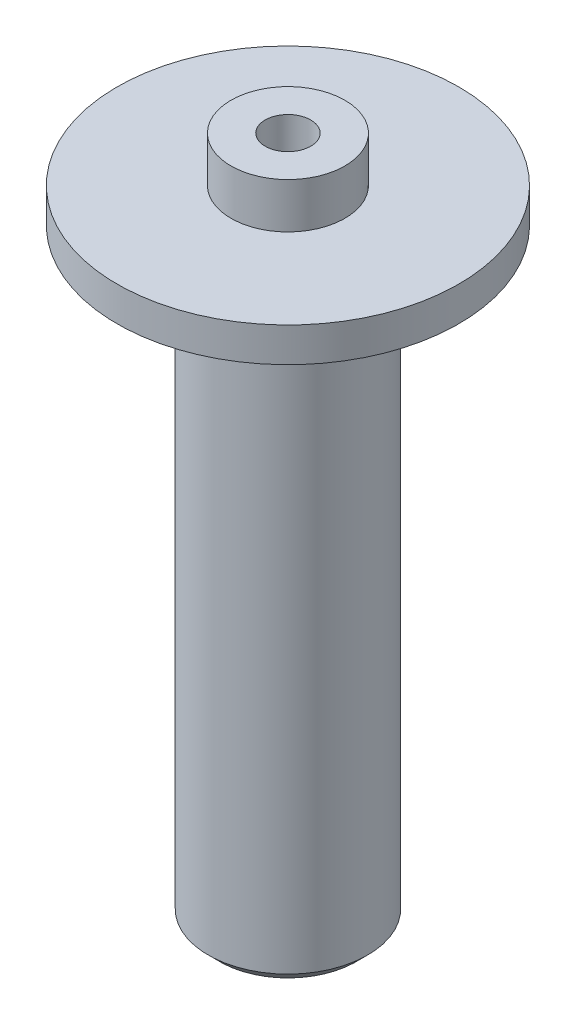
SolidWorks part; units mm, degrees
ref_plane "Спереди" through (0, 0, 0) normal (0, 0, 1) x (1, 0, 0)
ref_plane "Сверху" through (0, 0, 0) normal (0, 1, 0) x (1, 0, 0)
ref_plane "Справа" through (0, 0, 0) normal (1, 0, 0) x (0, 0, -1)
sketch "Эскиз1" plane through (0, 0, 0) normal (0, 0, 1) x (1, 0, 0)
  line L0 (2, 0) -> (2, 60)
  line L1 (2, 60) -> (5, 60)
  line L4 (5, 60) -> (5, 56.0159)
  line L5 (5, 56.0159) -> (15, 56.0159)
  line L6 (15, 56.0159) -> (15, 52.9943)
  line L7 (15, 52.9943) -> (7, 52.9943)
  line L8 (7, 52.9943) -> (7, 0)
  line L10 (7, 0) -> (2, 0)
  line L11 (0, -11.4414) -> (0, 79.8018) construction
  point P2 (0, 0)
  point P3 (0, 0)
  point P4 (10.9422, 61.5847)
  point P14 (11.1418, 61.5847)
  point P15 (10.8993, 61.5847)
  point P16 (10.8501, 61.5937)
  point P17 (4.151, 61.6102)
  point P18 (0, 0)
  point P19 (0, 0)
  point P20 (0, 0)
  point P21 (0, 0)
  point P22 (7, 0)
  point P23 (6.9686, -0.8922)
  point P24 (0, 0)
revolve "Повернуть1" add sketch "Эскиз1" angle 360 about L11
chamfer "Фаска1" distance 1 angle 45 1 edges at (0, 0, -7)
